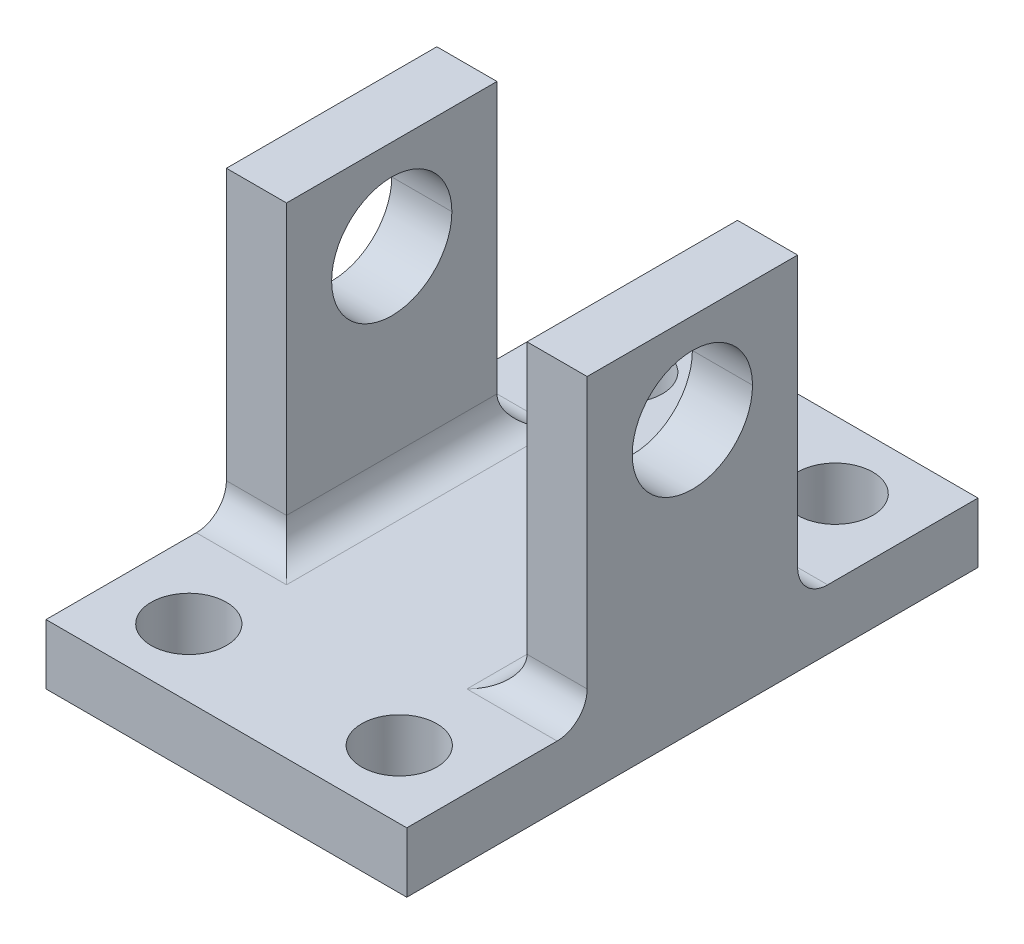
SolidWorks part; units mm, degrees
ref_plane "Front Plane" through (0, 0, 0) normal (0, 0, 1) x (1, 0, 0)
ref_plane "Top Plane" through (0, 0, 0) normal (0, 1, 0) x (1, 0, 0)
ref_plane "Right Plane" through (0, 0, 0) normal (1, 0, 0) x (0, 0, -1)
sketch "Sketch1" plane through (0, 0, 0) normal (0, 0, 1) x (1, 0, 0)
  line L0 (0, 0) -> (0, 24) construction
  line L1 (0, 24) -> (-4, 24)
  line L2 (-4, 24) -> (-4, 4)
  line L3 (-4, 4) -> (-20, 4)
  line L5 (-24, 0) -> (0, 0)
  line L6 (-24, 0) -> (-24, 24) construction
  line L7 (-24, 24) -> (-20, 24)
  line L8 (-20, 24) -> (-20, 4)
  line L12 (-24, 0) -> (-24, 24)
  line L16 (0, 0) -> (0, 24)
  dimension "D1" = 4
  dimension "D2" = 4
  dimension "D3" = 24
  dimension "D4" = 16
  dimension "D5" = 4
extrude "Boss-Extrude1" add sketch "Sketch1" along normal mid plane 38 contours L5 L16 L1 L2 L3 L8 L7 L12
sketch "Sketch2" plane through (-4, 0, 0) normal (-1, 0, 0) x (0, 0, 1)
  circle A0 centre (0, 18) radius 4
  dimension "D1" = 8
  dimension "D2" = 18
extrude "M8 hole" cut sketch "Sketch2" against normal through all both and the other way through all
sketch "Sketch3" plane through (0, 4, 0) normal (0, 1, 0) x (1, 0, 0)
  line L0 (0, 0) -> (-24, 0) construction
  line L1 (-24, -19) -> (-24, 19) construction
  line L2 (-12, 19) -> (-12, -19) construction
  line L3 (-4, 19) -> (-20, 19) construction
  line L4 (-4, -19) -> (-20, -19) construction
  circle A0 centre (-19, 14.5) radius 2.5
  circle A1 centre (-5, 14.5) radius 2.5
  circle A2 centre (-5, -14.5) radius 2.5
  circle A3 centre (-19, -14.5) radius 2.5
  dimension "D1" = 5
  dimension "D2" = 14.5
  dimension "D3" = 7
fillet "Fillet2" [suppressed] radius 5
extrude "M5 holes" cut sketch "Sketch3" against normal through all both and the other way through all
sketch "Sketch4" plane through (-24, 0, 0) normal (-1, 0, 0) x (0, 0, 1)
  line L0 (0, 0) -> (0, 24) construction
  line L1 (-19, 24) -> (-7, 24)
  line L2 (-19, 24) -> (-19, 4)
  line L3 (-19, 4) -> (-7, 4)
  line L4 (-7, 24) -> (-7, 4)
  line L9 (19, 0) -> (-19, 0) construction
  line L10 (19, 24) -> (-19, 24) construction
  line L11 (19, 4) -> (7, 4)
  line L12 (19, 24) -> (19, 4)
  line L13 (19, 24) -> (7, 24)
  line L14 (7, 24) -> (7, 4)
  dimension "D1" = 12
  dimension "D2" = 4
extrude "trim down sides" cut sketch "Sketch4" against normal through all
fillet "Fillet3" radius 2 6 edges at (-22, 4, -7) (-2, 4, -7) (-4, 4, 0) (-2, 4, 7) (-20, 4, 0) (-22, 4, 7)
ref_axis "Axis1" through (0, 18, 0) along (-1, 0, 0)
ref_plane "Plane1" through (0, 18, 0) normal (0, 1, 0) x (1, 0, 0)
split line "splitlineforFEA"
sketch "Sketch5" plane through (0, 4, 0) normal (0, 1, 0) x (1, 0, 0)
  circle A0 centre (-19, 14.5) radius 4.25
  dimension "D1" = 8.5
